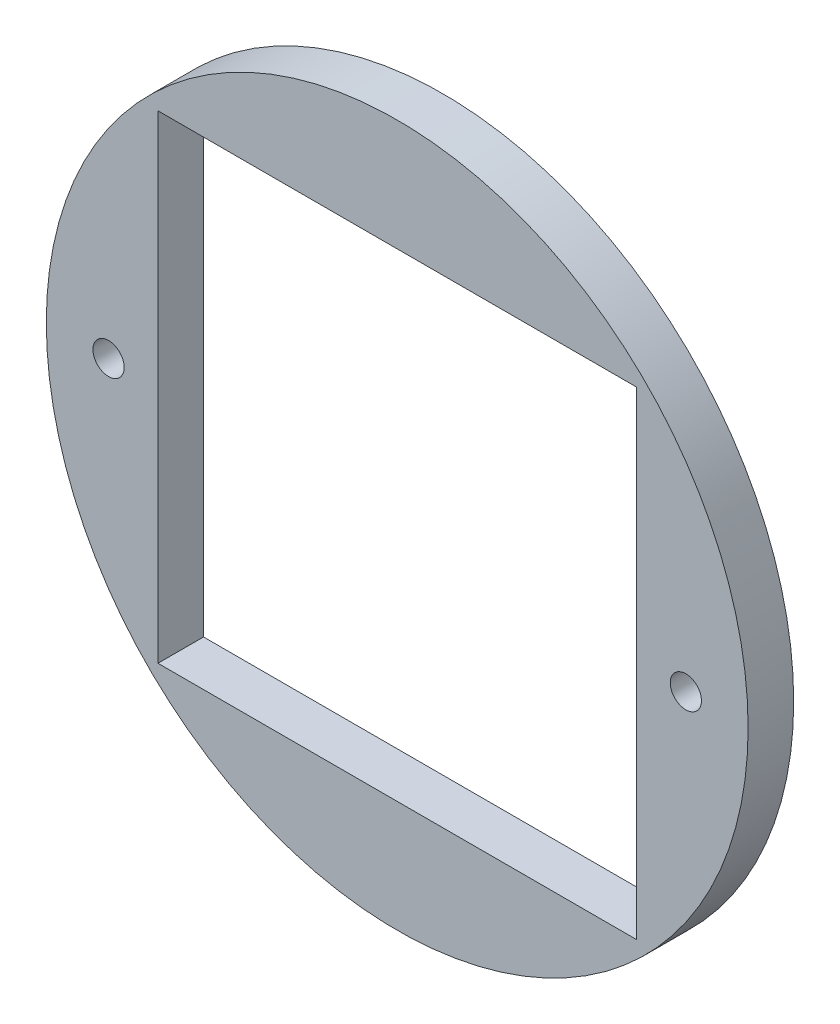
SolidWorks part; units mm, degrees
material "6061 Alloy"
ref_plane "Front Plane" through (0, 0, 0) normal (0, 0, 1) x (1, 0, 0)
ref_plane "Top Plane" through (0, 0, 0) normal (0, 1, 0) x (1, 0, 0)
ref_plane "Right Plane" through (0, 0, 0) normal (1, 0, 0) x (0, 0, -1)
sketch "Sketch1" plane through (0, 0, 0) normal (0, 0, 1) x (1, 0, 0)
  circle A0 centre (0, 0) radius 73.3425
  dimension "D1" = 146.685
extrude "Boss-Extrude1" add sketch "Sketch1" along normal blind 9.525
sketch "Sketch2" plane through (0, 0, 9.525) normal (0, 0, 1) x (1, 0, 0)
  point P0 (-60.325, 0)
  point P1 (60.325, 0)
  dimension "D1" = 60.325
  dimension "D2" = 60.325
hole_wizard "1/4 Clearance Hole1" positions "Sketch2" profile "Sketch3" hole size "1/4" standard "ANSI Inch" end condition through all
sketch "Sketch3" plane through (-60.325, 0, 9.525) normal (1, 0, 0) x (0, -1, 0)
  line L0 (0, 0) -> (0, 9.525)
  line L1 (0, 9.525) -> (3.2639, 9.525)
  line L2 (3.2639, 9.525) -> (3.2639, 0)
  line L5 (3.2639, 0) -> (0, 0)
  line L11 (0, -6.35) -> (0, 107.95) construction
  dimension "Thru Hole Dia." = 6.5278
  dimension "Thru Hole Depth" = 9.525
sketch "Sketch4" plane through (0, 0, 9.525) normal (0, 0, 1) x (1, 0, 0)
  line L1 (-50, -50) -> (50, -50)
  line L2 (-50, -50) -> (-50, 50)
  line L3 (-50, 50) -> (50, 50)
  line L4 (50, -50) -> (50, 50)
  line L5 (-50, -50) -> (50, 50) construction
  line L6 (-50, 50) -> (50, -50) construction
  point P0 (0, 0)
  dimension "D1" = 100
  dimension "D2" = 100
extrude "Cut-Extrude1" cut sketch "Sketch4" against normal through all both and the other way through all
equation "\"outerdiameter\"= 5.775"
equation "\"platethickness\"= 0.375"
equation "\"holespacing\"= 2.375"
equation "\"D1@Sketch1\"=\"outerdiameter\""
equation "\"D1@Boss-Extrude1\"=\"platethickness\""
equation "\"D1@Sketch2\"=\"holespacing\""
equation "\"D2@Sketch2\"=\"holespacing\""
equation "\"cutclearance\"= 100mm"
equation "\"D1@Sketch4\"=\"cutclearance\""
equation "\"D2@Sketch4\"=\"cutclearance\""
